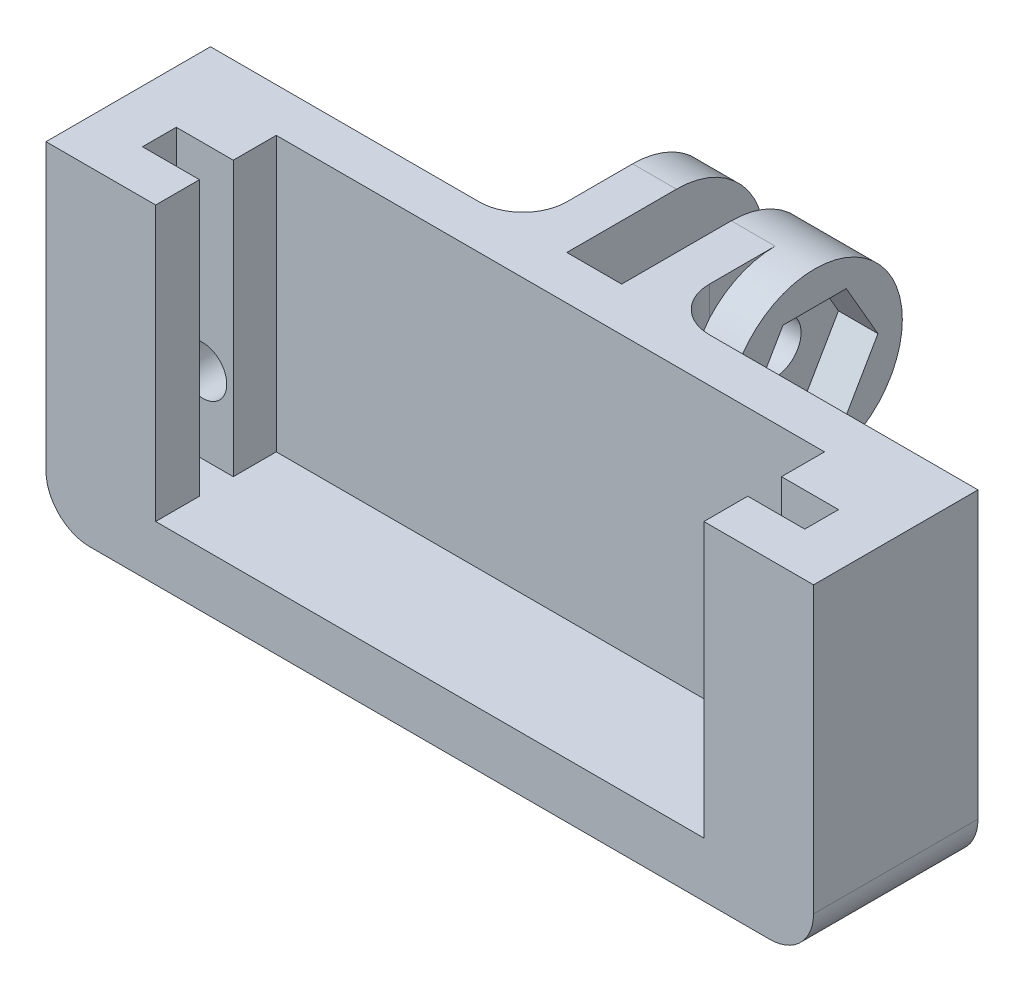
SolidWorks part; units mm, degrees
ref_plane "Front Plane" through (0, 0, 0) normal (0, 0, 1) x (1, 0, 0)
ref_plane "Top Plane" through (0, 0, 0) normal (0, 1, 0) x (1, 0, 0)
ref_plane "Right Plane" through (0, 0, 0) normal (1, 0, 0) x (0, 0, -1)
sketch "Sketch1" plane through (0, 0, 0) normal (0, 0, 1) x (1, 0, 0)
  line L1 (-22.225, 9.525) -> (22.225, 9.525)
  line L2 (-22.225, 9.525) -> (-22.225, -9.525)
  line L3 (-22.225, -9.525) -> (22.225, -9.525)
  line L4 (22.225, 9.525) -> (22.225, -9.525)
  line L5 (-22.225, 9.525) -> (22.225, -9.525) construction
  line L6 (-22.225, -9.525) -> (22.225, 9.525) construction
  point P0 (0, 0)
  dimension "D1" = 44.45
  dimension "D2" = 19.05
extrude "Boss-Extrude1" add sketch "Sketch1" along normal blind 6.985
sketch "Sketch4" plane through (0, 0, 0) normal (1, 0, 0) x (0, 0, -1)
  line L0 (0, 9.525) -> (6.35, 9.525)
  line L1 (6.35, -0.635) -> (0, -0.635)
  line L2 (0, -0.635) -> (0, 9.525)
  line L4 (0, -9.525) -> (0, 9.525) construction
  line L6 (-6.985, 9.525) -> (0, 9.525) construction
  arc A0 (6.35, 9.525) -> (6.35, -0.635) centre (6.35, 4.445) cw
  circle A1 centre (6.35, 4.445) radius 1.5
  dimension "D1" = 6.35
  dimension "D2" = 5.08
  dimension "D3" = 3
extrude "Boss-Extrude3" add sketch "Sketch4" along normal blind 2.54 from offset 1.5875
mirror "Mirror1" about plane through (0, 0, 0) normal (1, 0, 0) of "Boss-Extrude3"
sketch "Sketch5" plane through (4.1275, 0, 0) normal (1, 0, 0) x (0, 0, -1)
  line L1 (8.1831, 7.62) -> (4.5169, 7.62)
  line L2 (4.5169, 7.62) -> (2.6838, 4.445)
  line L3 (2.6838, 4.445) -> (4.5169, 1.27)
  line L4 (4.5169, 1.27) -> (8.1831, 1.27)
  line L5 (8.1831, 1.27) -> (10.0162, 4.445)
  line L6 (10.0162, 4.445) -> (8.1831, 7.62)
  circle A0 centre (6.35, 4.445) radius 5.08
  circle A1 centre (6.35, 4.445) radius 3.175 construction
  arc A2 (6.35, -0.635) -> (6.35, 9.525) centre (6.35, 4.445) ccw construction
  dimension "D1" = 6.35
extrude "Boss-Extrude4" add sketch "Sketch5" along normal blind 2.286
fillet "Fillet3" radius 2.54 2 edges at (-4.1275, 4.445, 0)
fillet "Fillet4" radius 2.54 2 edges at (-4.1275, -0.635, 0) (4.1275, -0.635, 0)
sketch "Sketch7" plane through (0, 0, 6.985) normal (0, 0, 1) x (1, 0, 0)
  line L0 (-22.225, -9.525) -> (22.225, -9.525) construction
  line L1 (-15.875, 9.525) -> (15.875, 9.525)
  line L2 (-15.875, 9.525) -> (-15.875, -6.35)
  line L3 (-15.875, -6.35) -> (15.875, -6.35)
  line L4 (15.875, 9.525) -> (15.875, -6.35)
  line L5 (-15.875, 9.525) -> (15.875, -6.35) construction
  line L6 (-15.875, -6.35) -> (15.875, 9.525) construction
  line L7 (22.225, 9.525) -> (-22.225, 9.525) construction
  point P0 (0, 1.5875)
  dimension "D1" = 31.75
  dimension "D2" = 3.175
extrude "Cut-Extrude1" cut sketch "Sketch7" against normal blind 4.445
sketch "Sketch8" plane through (0, 0, 6.985) normal (0, 0, 1) x (1, 0, 0)
  line L0 (-22.225, -9.525) -> (22.225, -9.525) construction
  line L1 (-19.177, 9.525) -> (19.177, 9.525)
  line L2 (-19.177, 9.525) -> (-19.177, -6.35)
  line L3 (-19.177, -6.35) -> (19.177, -6.35)
  line L4 (19.177, 9.525) -> (19.177, -6.35)
  line L5 (-19.177, 9.525) -> (19.177, -6.35) construction
  line L6 (-19.177, -6.35) -> (19.177, 9.525) construction
  line L7 (-15.875, 9.525) -> (-22.225, 9.525) construction
  point P0 (0, 1.5875)
  dimension "D1" = 38.354
  dimension "D2" = 3.175
extrude "Cut-Extrude2" cut sketch "Sketch8" against normal blind 1.9558
sketch "Sketch9" plane through (0, 0, 6.985) normal (0, 0, 1) x (1, 0, 0)
  line L0 (-22.225, 9.525) -> (-15.875, 9.525)
  line L1 (-15.875, 9.525) -> (-15.875, -6.35)
  line L2 (-15.875, -6.35) -> (15.875, -6.35)
  line L3 (15.875, -6.35) -> (15.875, 9.525)
  line L4 (15.875, 9.525) -> (22.225, 9.525)
  line L5 (22.225, 9.525) -> (22.225, -9.525)
  line L6 (22.225, -9.525) -> (-22.225, -9.525)
  line L7 (-22.225, -9.525) -> (-22.225, 9.525)
extrude "Boss-Extrude5" add sketch "Sketch9" along normal blind 2.54
fillet "Fillet5" radius 2.54 2 edges at (22.225, -9.525, 4.7625) (-22.225, -9.525, 4.7625)
sketch "Sketch12" plane through (0, 0, 0) normal (0, 0, -1) x (-1, 0, 0)
  line L0 (-17.653, -1.905) -> (17.653, -1.905) construction
  line L1 (-22.225, -6.985) -> (-22.225, 9.525) construction
  line L2 (19.685, -9.525) -> (-19.685, -9.525) construction
  circle A0 centre (-17.653, -1.905) radius 1.4
  circle A1 centre (17.653, -1.905) radius 1.4
  point P4 (0, -1.905)
  dimension "D1" = 4.572
  dimension "D2" = 2.8
  dimension "D3" = 7.62
extrude "Cut-Extrude5" cut sketch "Sketch12" against normal up to surface (6.985 mm away) up to face at (17.526, 1.5875, 6.985)
